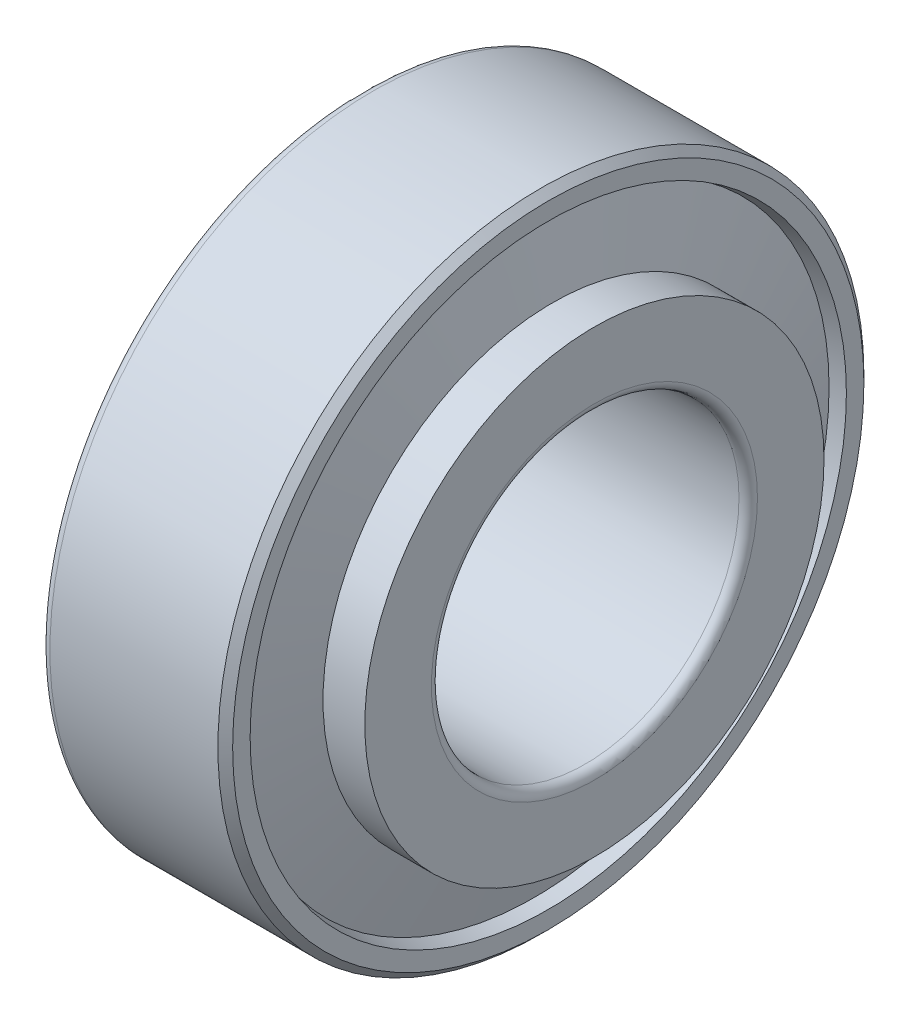
SolidWorks part; units mm, degrees
revolve "OuterRace" add sketch "OutRacSke" angle 360 about L5 other way angle 28.04 reverse direction yes
sketch "OutRacSke" plane through (0, 0, 0) normal (0, 0, 1) x (1, 0, 0)
  line L0 (-3, 19.3824) -> (-15, 16.3905)
  line L1 (-15, 16.3905) -> (-15, 20.4)
  line L2 (-14.4, 21) -> (-3.48, 21)
  line L3 (-3.48, 21) -> (-3, 20.52)
  line L4 (-3, 20.52) -> (-3, 19.3824)
  line L5 (-42.5, 0) -> (42.5, 0) construction
  arc A0 (-15, 20.4) -> (-14.4, 21) centre (-14.4, 20.4) cw
  dimension "D8" = 45
  dimension "Tangle" = 14
ref_plane "Plane1" through (0, 0, 0) normal (0, 0, 1) x (1, 0, 0)
ref_plane "Plane2" through (0, 0, 0) normal (0, 1, 0) x (1, 0, 0)
ref_plane "Plane3" through (0, 0, 0) normal (1, 0, 0) x (0, 0, -1)
sketch "Clipboard" plane through (0, 0, 0) normal (0, 0, 1) x (1, 0, 0)
  line L0 (0, 0) -> (10, 0) construction
  line L1 (0, 0) -> (32.761, -1.144)
  line L2 (0, 0) -> (19.9878, 0.698)
  line L3 (0, 0) -> (41.9744, -1.4658)
  line L4 (0, 0) -> (-10.7984, -0.1885)
  line L5 (0, 0) -> (-4.95, 15)
  dimension "Roller_diameter" = 4.95
  dimension "cyl_len" = 10.8
sketch "RolDetSke" plane through (0, 0, 0) normal (0, 0, 1) x (1, 0, 0)
  line L0 (-13.8012, 14.2213) -> (-14.4, 16.6228)
  line L1 (-13.8012, 14.2213) -> (-3.322, 16.8341)
  line L2 (-3.9208, 19.2356) -> (-3.322, 16.8341)
  line L4 (-38.2092, 8.1357) -> (11.672, 20.5725) construction
  line L5 (-3.9208, 19.2356) -> (-14.4, 16.6228)
  line L9 (-3, 19.3824) -> (-15, 16.3905) construction
  dimension "Roller_diameter" = 4.95
  dimension "dy" = 16.6228
  dimension "D2" = 14.4
  dimension "cyl_len" = 10.8
revolve "RollerDetailed" [suppressed] add sketch "RolDetSke" angle 360 about L4 reverse direction yes
sketch "RolSimSke" plane through (0, 0, 0) normal (0, 0, 1) x (1, 0, 0)
  line L0 (0, 0) -> (-32, 0) construction
  line L1 (-14.4, 16.6228) -> (-3.9208, 19.2356)
  line L2 (-14.4, 16.6228) -> (-13.2025, 11.8198)
  line L3 (-13.2025, 11.8198) -> (-2.7233, 14.4326)
  line L4 (-3.9208, 19.2356) -> (-2.7233, 14.4326)
  dimension "Roller_diameter" = 4.95
  dimension "dy" = 16.6228
  dimension "dx" = 14.4
  dimension "Tangle" = 14
revolve "RollersSimplified" add sketch "RolSimSke" angle 360 about L0
ref_axis "Axis1" through (-50, 0, 0) along (1, 0, 0)
pattern_circular "RollersDetailed" [suppressed] count 2 every 180 about axis through (-50, 0, 0) along (1, 0, 0)
sketch "InsRacSke" plane through (0, 0, 0) normal (0, 0, 1) x (1, 0, 0)
  line L0 (-13.2582, 12.0673) -> (-15, 12.0673)
  line L1 (-15, 20.4) -> (-15, -20.4) construction
  line L2 (-15, 12.0673) -> (-15, 10.48)
  line L3 (-15, 10.48) -> (-14.52, 10)
  line L4 (-14.52, 10) -> (-0.6, 10)
  line L5 (0, 10.6) -> (0, 14.9276)
  line L6 (0, 14.9276) -> (-2.7173, 14.9276)
  line L7 (-2.7173, 14.9276) -> (-2.7173, 14.4326)
  line L8 (-2.7173, 14.4326) -> (-13.1965, 11.8198)
  line L9 (-13.1965, 11.8198) -> (-13.2582, 12.0673)
  line L10 (-42.5, 0) -> (42.5, 0) construction
  arc A0 (-0.6, 10) -> (0, 10.6) centre (-0.6, 10.6) ccw
  dimension "Tangle" = 14
  dimension "cyl_len" = 10.8
  dimension "dy" = 11.8198
  dimension "dx" = 13.1965
  dimension "D11" = 45
  dimension "D2" = 15
revolve "InnerRace" add sketch "InsRacSke" angle 360 about L10 reverse direction yes
sketch "CagSpiSke" plane through (0, 0, 0) normal (0, 0, 1) x (1, 0, 0)
  line L3 (-2.7981, 16.882) -> (-13.8012, 14.1386)
  line L4 (-14.0416, 13.7386) -> (-13.8819, 13.0982)
  line L6 (-42.5, 0) -> (42.5, 0) construction
  arc A1 (-13.8012, 14.1386) -> (-14.0416, 13.7386) centre (-13.7214, 13.8184) ccw
  dimension "Tangle" = 14
  dimension "radius" = 0.33
  dimension "dx" = 13.8012
  dimension "dy" = 14.1386
  dimension "offset" = 0.99
revolve "CageSpine" [suppressed] add sketch "CagSpiSke" angle 0.001 about L6 wall 0.825
equation "\"OD@OutRacSke\" = \"Race_OD@Clipboard\""
equation "\"cup_SID@OutRacSke\" = \"Race_ID@Clipboard\""
equation "\"chamfer@OutRacSke\" = \"cup_width@OutRacSke\" / 25"
equation "\"offset@OutRacSke\" = \"OA_width@Clipboard\""
equation "\"D2@RolDetSke\" = \"offset@OutRacSke\" - \"cup_radius@OutRacSke\""
equation "\"dy@RolDetSke\" =  ( ( \"Race_ID@Clipboard\" / 2 ) + ( \"cup_radius@OutRacSke\" ) * tan(\"Tangle@OutRacSke\" * 3.141592654/180) ) * 1.005"
equation "\"cyl_len@RolDetSke\" = \"cyl_len@Clipboard\""
equation "\"Roller_diameter@RolDetSke\" = \"Roller_diameter@Clipboard\""
equation "\"dx@RolSimSke\" = \"offset@OutRacSke\" - \"cup_radius@OutRacSke\""
equation "\"dy@RolSimSke\" =  ( ( \"Race_ID@Clipboard\" / 2 ) + ( \"cup_radius@OutRacSke\" ) * tan(\"Tangle@OutRacSke\" * 3.141592654/180) ) * 1.005"
equation "\"Cyl_Len@RolSimSke\" = \"cyl_len@Clipboard\""
equation "\"Roller_diameter@RolSimSke\" = \"Roller_diameter@Clipboard\""
equation "\"Bore@InsRacSke\" = \"Bore@Clipboard\""
equation "\"Tangle@InsRacSke\" = \"Tangle@OutRacSke\""
equation "\"cyl_len@InsRacSke\" = \"cyl_len@Clipboard\""
equation "\"chamfer@InsRacSke\" = \"chamfer@OutRacSke\""
equation "\"D2@InsRacSke\" = \"OA_width@Clipboard\""
equation "\"dx@InsRacSke\" = \"offset@OutRacSke\" - \"cup_radius@OutRacSke\" -  (  \"Roller_diameter@Clipboard\" * 1.005 )  * sin(\"Tangle@InsRacSke\" * 3.141592654/180)"
equation "\"dy@InsRacSke\" = ( ( \"Race_ID@Clipboard\" / 2 ) + ( \"cup_radius@OutRacSke\" ) * tan(\"Tangle@OutRacSke\" * 3.141592654/180) ) * 1.005 -  ( \"Roller_diameter@Clipboard\" )  * cos(\"Tangle@InsRacSke\" * 3.141592654/180) "
equation "\"front_groove@InsRacSke\" = \"Groove_dp@InsRacSke\" / 2"
equation "\"Tangle@CagSpiSke\" = \"Tangle@OutRacSke\""
equation "\"dx@CagSpiSke\" = ( \"offset@OutRacSke\" - \"cup_radius@OutRacSke\" ) -  (  \"Roller_diameter@Clipboard\" / 2  )  * sin(\"Tangle@InsRacSke\" * 3.141592654/180)"
equation "\"dy@CagSpiSke\" = ( ( \"Race_ID@Clipboard\" / 2 ) + ( \"cup_radius@OutRacSke\" ) * tan(\"Tangle@OutRacSke\" * 3.141592654/180) )  -  ( \"Roller_diameter@Clipboard\" / 2 )  * cos(\"Tangle@InsRacSke\" * 3.141592654/180) "
equation "\"length@CagSpiSke\" = \"cyl_len@Clipboard\" * 1.05"
equation "\"offset@CagSpiSke\" = \"Roller_diameter@Clipboard\" / 5"
equation "\"radius@CagSpiSke\" = \"offset@CagSpiSke\" / 3"
equation "\"D3@CageSpine\" = \"Roller_diameter@Clipboard\" / 6"
equation "\"Max_count@Clipboard\" = int( 3.14159265 / atn(( \"Roller_diameter@Clipboard\" / 2) / sqr( \"dy@CagSpiSke\"  *  \"dy@CagSpiSke\" - ( \"Roller_diameter@Clipboard\" / 2) *  ( \"Roller_diameter@Clipboard\" / 2))))"
equation "\"Max_count@Clipboard\" = ((sgn( \"Max_count@Clipboard\" - \"Count@Clipboard\" )-1)*( \"Max_count@Clipboard\" - \"Count@Clipboard\" ))/-2+ \"Count@Clipboard\""
equation "\"Count@RollersDetailed\" = int( \"Show_count@Clipboard\" ) "
equation "\"Count@RollersDetailed\" = ((sgn( \"Count@RollersDetailed\" - \"Max_count@Clipboard\" )-1)*( \"Count@RollersDetailed\" - \"Max_count@Clipboard\" ))/-2+ \"Max_count@Clipboard\""
equation "\"Count@RollersDetailed\" = ((sgn( \"Count@RollersDetailed\" - \"Min_count@Clipboard\" )+1)*( \"Count@RollersDetailed\" - \"Min_count@Clipboard\"))/2 +\"Min_count@Clipboard\""
equation "\"Angle@RollersDetailed\" = 360.0 / \"Max_count@Clipboard\""
equation "\"Angle@CageSpine\" =  \"Angle@RollersDetailed\" * ( \"Count@RollersDetailed\" -1 + int( \"Count@RollersDetailed\" / \"Max_count@Clipboard\" ) )  + 0.001 -  int( \"Count@RollersDetailed\" / \"Max_count@Clipboard\" ) * 0.001"
equation "\"Angle@CageSpine\" =  \"Angle@CageSpine\" * int( \"Min_count@Clipboard\" / 2) + int(1 / \"Min_count@Clipboard\")  * 0.001"
equation "\"Tangle@RolSimSke\" = \"Tangle@OutRacSke\""
